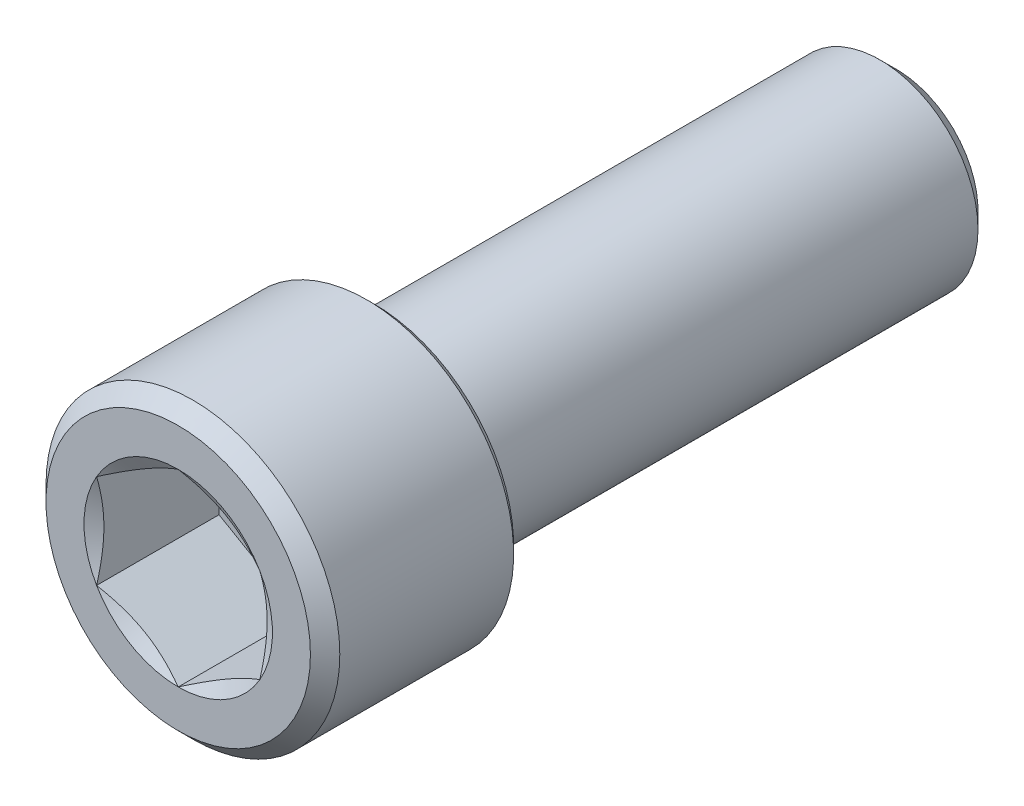
SolidWorks part; units mm, degrees
ref_plane "Front Plane" through (0, 0, 0) normal (0, 0, 1) x (1, 0, 0)
ref_plane "Top Plane" through (0, 0, 0) normal (0, 1, 0) x (1, 0, 0)
ref_plane "Right Plane" through (0, 0, 0) normal (1, 0, 0) x (0, 0, -1)
sketch "Sketch1" plane through (0, 0, 0) normal (1, 0, 0) x (0, 0, -1)
  line L0 (17.4625, 0) -> (-17.4625, 0) construction
  line L1 (-17.4625, 0) -> (-17.4625, 7.1437) construction
  line L2 (-7.9375, 4.7625) -> (-7.9375, 0) construction
  line L3 (16.4042, 0) -> (16.4042, 1.0583) construction
  line L4 (-7.9375, 0) -> (-7.9375, -4.7625) construction
  line L5 (17.4625, 4.7625) -> (17.4625, -4.7625) construction
  line L6 (-7.9375, 4.7625) -> (-7.9375, 7.1437) construction
  point P6 (-17.4625, 3.9687)
  point P9 (-17.4625, -3.9688)
  point P10 (-7.9375, 0)
  point P13 (13.7583, -4.7625)
  dimension "D1" = 1.0583
  dimension "D2" = 3.7042
sketch "Sketch2" plane through (0, 0, 0) normal (1, 0, 0) x (0, 0, -1)
  line L0 (17.4625, 3.9687) -> (16.6687, 4.7625)
  line L1 (-17.4625, 7.1437) -> (-7.9375, 7.1437)
  line L2 (-17.4625, 7.1437) -> (-17.4625, 0)
  line L4 (-7.9375, 7.1437) -> (-7.9375, 4.7625)
  line L5 (-7.9375, 4.7625) -> (16.6687, 4.7625)
  line L8 (17.4625, 3.9687) -> (17.4625, 0)
  line L9 (17.4625, 0) -> (-17.4625, 0) construction
  line L10 (17.4625, 0) -> (-17.4625, 0)
  dimension "D1" = 135
  dimension "D2" = 0.7938
revolve "Revolve1" add sketch "Sketch2" angle 360 about L10
sketch "Sketch4" plane through (0, 0, 17.4625) normal (0, 0, 1) x (1, 0, 0)
  line L1 (0, 4.5827) -> (-3.9688, 2.2914)
  line L2 (-3.9688, 2.2914) -> (-3.9687, -2.2914)
  line L3 (-3.9687, -2.2914) -> (0, -4.5827)
  line L4 (0, -4.5827) -> (3.9688, -2.2914)
  line L5 (3.9688, -2.2914) -> (3.9688, 2.2914)
  line L6 (3.9688, 2.2914) -> (0, 4.5827)
  circle A0 centre (0, 0) radius 3.9688 construction
  circle A1 centre (0, 0) radius 7.1437 construction
  circle A2 centre (0, 0) radius 7.1437 construction
  dimension "D1" = 7.9375
extrude "Cut-Extrude1" cut sketch "Sketch4" against normal blind 5.9531
sketch "Sketch5" plane through (0, 0, 17.4625) normal (0, 0, 1) x (1, 0, 0)
  circle A0 centre (0, 0) radius 4.5827
extrude "Cut-Extrude2" cut sketch "Sketch5" against normal blind 10 draft 60
chamfer "Chamfer1" distance 0.7144 angle 45 1 edges at (-7.1437, 0, 17.4625)
chamfer "Chamfer2" distance 0.3572 angle 45 1 edges at (-7.1437, 0, 7.9375)
sketch "Sketch3" [suppressed] plane through (0, 0, -17.4625) normal (0, 0, -1) x (-1, 0, 0)
  circle A0 centre (0, 0) radius 4.7625 construction
  circle A1 centre (0, 0) radius 4.7625
ref_axis "Center Axis1" through (0, 0, -5.7305) along (0, 0, 1)
ref_plane "Contact Plane1" through (0, 0, -17.4625) normal (0, 0, 1) x (1, 0, 0)
ref_plane "Contact Plane2" through (0, 0, 7.9375) normal (0, 0, 1) x (1, 0, 0)
ref_plane "Plane1" [suppressed] through (0, 0, 7.8052) normal (0, 0, -1) x (-1, 0, 0)
split "Split1" [suppressed] bodies to split 106
curve "Helix/Spiral1" [suppressed] pitch 1.0583 height 26.4583 turns 25
sketch "Sketch7" [suppressed] plane through (0, 0, 0) normal (1, 0, 0) x (0, 0, -1)
  line L0 (17.3964, 4.8771) -> (17.9255, 3.9605) construction
  line L1 (17.9255, 3.9605) -> (18.4547, 4.8771) construction
  line L2 (18.4547, 4.8771) -> (17.3964, 4.8771) construction
  line L3 (17.4625, 4.7625) -> (18.3885, 4.7625)
  line L4 (17.9255, 4.8771) -> (17.9255, 4.7625) construction
  line L5 (17.9255, 4.7625) -> (17.9255, 4.0751) construction
  line L6 (17.9255, 4.0751) -> (17.9255, 3.9605) construction
  line L7 (17.8594, 4.0751) -> (17.9917, 4.0751)
  line L9 (17.9917, 4.0751) -> (18.3885, 4.7625)
  line L10 (17.8594, 4.0751) -> (17.4625, 4.7625)
  line L11 (16.4042, 0) -> (16.4042, 1.0583) construction
  line L13 (17.4625, -4.7625) -> (17.4625, 4.7625)
  line L14 (17.4625, -4.7625) -> (17.4625, 4.7625) construction
  dimension "D2" = 0.1323
sweep "Cut-Sweep1" [suppressed] cut profiles "Sketch7" path "Helix/Spiral1"
sketch "Sketch12" [suppressed] plane through (0, 0, 7.8052) normal (0, 0, -1) x (-1, 0, 0)
  circle A0 centre (0, 0) radius 4.8683
  circle A1 centre (0, 0) radius 4.7625
  circle A2 centre (0, 0) radius 4.7625 construction
  dimension "D2" = 0.1058
extrude "Boss-Extrude5" [suppressed] add sketch "Sketch12" against normal up to surface (0.1323 mm away)
sketch "Sketch11" [suppressed] plane through (0, 0, 7.8052) normal (0, 0, -1) x (-1, 0, 0)
  circle A2 centre (0, 0) radius 4.8683
  circle A3 centre (0, 0) radius 4.8683
  dimension "D1" = 0
extrude "Boss-Extrude4" [suppressed] add sketch "Sketch11" along normal through all draft 59.674
sketch "Sketch9" [suppressed] plane through (0, 0, 7.9375) normal (0, 0, -1) x (-1, 0, 0)
  line L0 (0, 0) -> (0, 7.1437) construction
  line L1 (0, 6.7866) -> (-0.7488, 7.5009)
  line L2 (-0.7488, 7.5009) -> (0.7488, 7.5009)
  line L3 (0.7488, 7.5009) -> (0, 6.7866)
  line L4 (-0.3744, 7.1437) -> (0, 0) construction
  line L5 (0, 0) -> (0.3744, 7.1437) construction
  circle A0 centre (0, 0) radius 7.1437 construction
  circle A1 centre (0, 0) radius 6.7866 construction
  dimension "D1" = 0.7144
  dimension "D2" = 6
extrude "Cut-Extrude3" [suppressed] cut sketch "Sketch9" against normal up to next
pattern_circular "CirPattern1" [suppressed] count 60 over 360 of bodies 112
equation "\"Pitch Natural Taper Angle\"= ATN ( \"Pitch@Sketch1\" / 2 )"
equation "\"Rounded Angle Count\"= ROUND ( 60 / \"Pitch Natural Taper Angle\" )"
equation "\"Taper Angle\"= \"Rounded Angle Count\" * \"Pitch Natural Taper Angle\""
equation "\"D1@Sketch1\"=\"Pitch@Sketch1\""
equation "\"D2@Sketch2\"=\"D1@Sketch1\"*.75"
equation "\"D4@Helix/Spiral1\"=\"Pitch@Sketch1\""
equation "\"D3@Helix/Spiral1\"=\"Length@Sketch1\"+\"Pitch@Sketch1\""
equation "\"D1@Sketch4\" = \"Drive Size@Sketch1\""
equation "\"D1@Cut-Extrude1\"=\"D1@Sketch4\"*.75"
equation "\"D1@Chamfer1\" = \"Head Diameter@Sketch1\" * .05"
equation "\"D1@Chamfer2\"=\"D1@Chamfer1\"/2"
equation "\"D2@Sketch7\"=\"Pitch@Sketch1\"*0.125"
equation "\"D2@Sketch1\"=\"Pitch@Sketch1\"*3.5"
equation "\"D1@Sketch9\"=\"D1@Chamfer1\""
equation "\"D1@CirPattern1\"=\"D3@CirPattern1\"/\"D2@Sketch9\""
equation "\"D1@Plane1\"=\"Pitch@Sketch1\"*0.125"
equation "\"D3@Boss-Extrude4\"=\"Taper Angle\""
equation "\"D2@Sketch12\"=\"Pitch@Sketch1\"*0.1"
